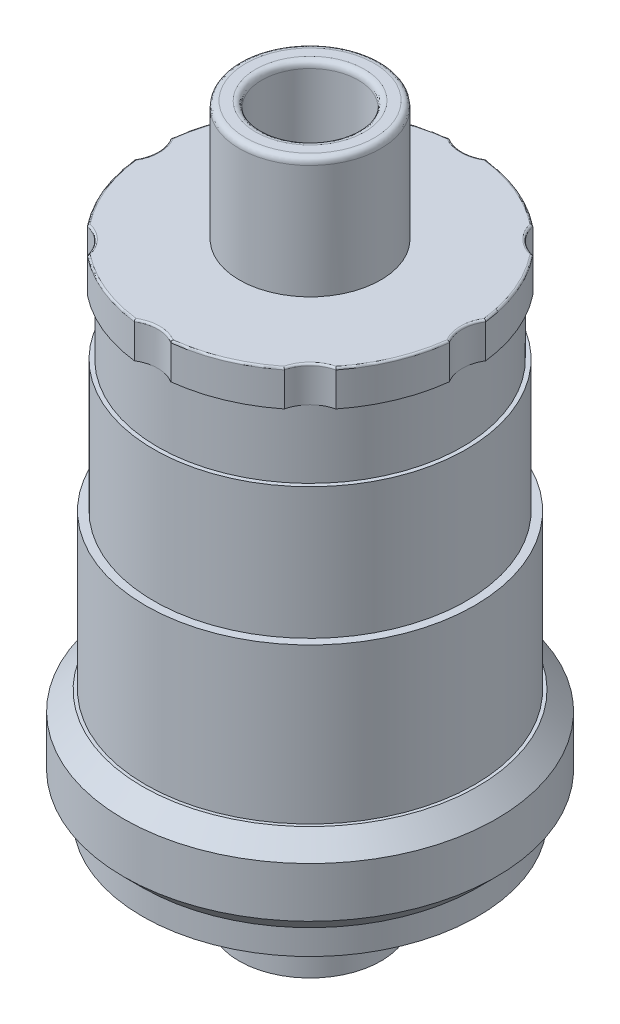
SolidWorks part; units mm, degrees
ref_plane "Front Plane" through (0, 0, 0) normal (0, 0, 1) x (1, 0, 0)
ref_plane "Top Plane" through (0, 0, 0) normal (0, 1, 0) x (1, 0, 0)
ref_plane "Right Plane" through (0, 0, 0) normal (1, 0, 0) x (0, 0, -1)
sketch "Sketch1" plane through (0, 0, 0) normal (1, 0, 0) x (0, 0, -1)
  line L0 (0, 19.2318) -> (0, -17.608) construction
  line L1 (0, -13.9545) -> (11.35, -13.9545)
  line L2 (11.35, -13.9545) -> (11.35, -0.0545)
  line L3 (0, -0.0545) -> (0, -8.2545)
  line L4 (0, -13.9545) -> (0, -8.2545)
  line L17 (11.35, -0.0545) -> (0, -0.0545) construction
  line L18 (10.25, -8.2545) -> (0, -8.2545)
  line L19 (10.25, -13.9545) -> (10.25, -8.2545)
  line L20 (11.35, -0.0545) -> (0, -0.0545)
  line L21 (0, -0.0545) -> (11.35, -0.0545)
  dimension "D1" = 10.25
  dimension "D2" = 13.9
  dimension "D4" = 5.7
  dimension "D5" = 1.1
revolve "Revolve1" add sketch "Sketch1" angle 360 about L0 region at (0, -4.5931, -5.9985)
sketch "Sketch2" plane through (0, -8.2545, 0) normal (0, -1, 0) x (1, 0, 0)
  line L0 (0, 10.25) -> (0, -10.25) construction
  line L1 (-10.25, 0) -> (10.25, 0) construction
  circle A0 centre (0, 0) radius 3.3
  circle A1 centre (0, 0) radius 10.25 construction
  circle A2 centre (0, 0) radius 10.25 construction
  circle A3 centre (0, 6.6954) radius 1.9
  circle A4 centre (4.7344, 4.7344) radius 1.9
  circle A5 centre (6.6954, 0) radius 1.9
  circle A6 centre (4.7344, -4.7344) radius 1.9
  circle A7 centre (0, -6.6954) radius 1.9
  circle A8 centre (-4.7344, -4.7344) radius 1.9
  circle A9 centre (-6.6954, 0) radius 1.9
  circle A10 centre (-4.7344, 4.7344) radius 1.9
  point P31 (0, 0)
  dimension "D1" = 6.6
  dimension "D2" = 3.8
  dimension "D3" = 8
extrude "Cut-Extrude1" cut sketch "Sketch2" against normal blind 5
sketch "Sketch5" plane through (0, -0.0545, 0) normal (0, 1, 0) x (1, 0, 0)
  circle A0 centre (0, 0) radius 26.8
  dimension "D1" = 53.6
extrude "Boss-Extrude3" add sketch "Sketch5" along normal blind 4
sketch "Sketch7" plane through (0, 3.9455, 0) normal (0, 1, 0) x (1, 0, 0)
  circle A0 centre (0, 0) radius 26.8
extrude "Boss-Extrude4" add sketch "Sketch7" along normal blind 3 draft 45 draft outward yes
sketch "Sketch8" plane through (0, 6.9455, 0) normal (0, 1, 0) x (1, 0, 0)
  circle A0 centre (0, 0) radius 29.8
extrude "Boss-Extrude5" add sketch "Sketch8" along normal blind 8
sketch "Sketch9" plane through (0, 14.9455, 0) normal (0, 1, 0) x (1, 0, 0)
  circle A0 centre (0, 0) radius 29.8
extrude "Boss-Extrude6" add sketch "Sketch9" along normal blind 3 draft 45
sketch "Sketch10" plane through (0, 17.9455, 0) normal (0, 1, 0) x (1, 0, 0)
  circle A0 centre (0, 0) radius 26.3
  dimension "D1" = 52.6
extrude "Boss-Extrude7" add sketch "Sketch10" along normal blind 24.8
sketch "Sketch11" plane through (0, 42.7455, 0) normal (0, 1, 0) x (1, 0, 0)
  circle A1 centre (0, 0) radius 25
  dimension "D1" = 50
extrude "Boss-Extrude8" add sketch "Sketch11" along normal blind 21
sketch "Sketch12" plane through (0, 63.7455, 0) normal (0, 1, 0) x (1, 0, 0)
  circle A0 centre (0, 0) radius 24.35
  dimension "D1" = 48.7
extrude "Boss-Extrude9" add sketch "Sketch12" along normal blind 10.9
sketch "Sketch13" plane through (0, 74.6455, 0) normal (0, 1, 0) x (1, 0, 0)
  arc A0 (-19.8613, 15.7528) -> (-25.183, 2.9052) centre (0, 0) ccw
  arc A2 (-2.9052, 25.183) -> (2.9052, 25.183) centre (0, 29.8328) ccw
  arc A3 (15.7528, 19.8613) -> (19.8613, 15.7528) centre (21.095, 21.095) ccw
  arc A4 (25.183, 2.9052) -> (25.183, -2.9052) centre (29.8328, 0) ccw
  arc A5 (19.8613, -15.7528) -> (15.7528, -19.8613) centre (21.095, -21.095) ccw
  arc A6 (2.9052, -25.183) -> (-2.9052, -25.183) centre (0, -29.8328) ccw
  arc A7 (-15.7528, -19.8613) -> (-19.8613, -15.7528) centre (-21.095, -21.095) ccw
  arc A8 (-25.183, -2.9052) -> (-25.183, 2.9052) centre (-29.8328, 0) ccw
  arc A9 (-19.8613, 15.7528) -> (-15.7528, 19.8613) centre (-21.095, 21.095) ccw
  arc A16 (-25.183, -2.9052) -> (-19.8613, -15.7528) centre (0, 0) ccw
  arc A17 (-15.7528, -19.8613) -> (-2.9052, -25.183) centre (0, 0) ccw
  arc A18 (2.9052, -25.183) -> (15.7528, -19.8613) centre (0, 0) ccw
  arc A19 (19.8613, -15.7528) -> (25.183, -2.9052) centre (0, 0) ccw
  arc A20 (25.183, 2.9052) -> (19.8613, 15.7528) centre (0, 0) ccw
  arc A21 (15.7528, 19.8613) -> (2.9052, 25.183) centre (0, 0) ccw
  arc A22 (-2.9052, 25.183) -> (-15.7528, 19.8613) centre (0, 0) ccw
  point P22 (0, 0)
  dimension "D1" = 50.7
  dimension "D2" = 8
extrude "Boss-Extrude11" add sketch "Sketch13" along normal blind 5.7
fillet "Fillet1" radius 0.3 16 edges at (-24.35, 80.3455, 0) (-23.4203, 80.3455, 9.701) (-17.2181, 80.3455, 17.2181) (-9.701, 80.3455, 23.4203) (0, 80.3455, 24.35) (9.701, 80.3455, 23.4203) (17.2181, 80.3455, 17.2181) (23.4203, 80.3455, 9.701) (24.35, 80.3455, 0) (23.4203, 80.3455, -9.701) (17.2181, 80.3455, -17.2181) (9.701, 80.3455, -23.4203) (0, 80.3455, -24.35) (-9.701, 80.3455, -23.4203) (-17.2181, 80.3455, -17.2181) (-23.4203, 80.3455, -9.701)
sketch "Sketch15" plane through (0, 80.3455, 0) normal (0, 1, 0) x (1, 0, 0)
  circle A0 centre (0, 0) radius 11.3
  dimension "D1" = 22.6
extrude "Boss-Extrude12" add sketch "Sketch15" along normal blind 19.2
sketch "Sketch17" plane through (0, 99.5455, 0) normal (0, 1, 0) x (1, 0, 0)
  circle A0 centre (0, 0) radius 7.7
  dimension "D1" = 15.4
extrude "Cut-Extrude3" cut sketch "Sketch17" against normal blind 20.2
fillet "Fillet3" radius 1 2 edges at (0, 99.5455, 7.7) (0, 99.5455, 11.3) conic rho 0.5
